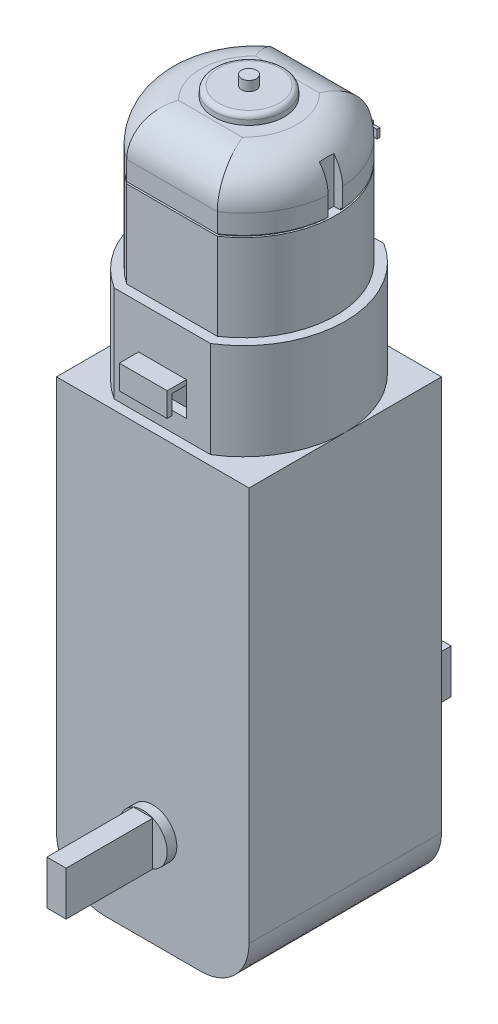
SolidWorks part; units mm, degrees
other "Camera1"
ref_plane "Front Plane" through (0, 0, 0) normal (0, 0, 1) x (1, 0, 0)
ref_plane "Top Plane" through (0, 0, 0) normal (0, 1, 0) x (1, 0, 0)
ref_plane "Right Plane" through (0, 0, 0) normal (1, 0, 0) x (0, 0, -1)
sketch "Sketch1" plane through (0, 0, 0) normal (0, 1, 0) x (1, 0, 0)
  line L1 (-5.5265, 6.0603) -> (14.4735, 6.0603)
  line L2 (-5.5265, 6.0603) -> (-5.5265, -13.9397)
  line L3 (-5.5265, -13.9397) -> (14.4735, -13.9397)
  line L4 (14.4735, 6.0603) -> (14.4735, -13.9397)
  dimension "D1" = 20
  dimension "D2" = 20
extrude "Boss-Extrude1" add sketch "Sketch1" along normal blind 46
sketch "Sketch2" plane through (0, 46, 0) normal (0, 1, 0) x (1, 0, 0)
  line L0 (14.4735, 6.0603) -> (-5.5265, 6.0603) construction
  line L1 (4.4735, 5.0603) -> (4.4735, 6.0603) construction
  line L2 (-0.5265, 5.0603) -> (9.4735, 5.0603)
  line L3 (14.4735, -3.9397) -> (-5.5265, -3.9397) construction
  line L4 (14.4735, -13.9397) -> (14.4735, 6.0603) construction
  line L5 (-5.5265, 6.0603) -> (-5.5265, -13.9397) construction
  line L6 (-0.5265, -12.9397) -> (9.4735, -12.9397)
  arc A0 (9.4735, 5.0603) -> (9.4735, -12.9397) centre (3.8735, -3.9397) cw
  arc A1 (-0.5265, -12.9397) -> (-0.5265, 5.0603) centre (5.0735, -3.9397) cw
  dimension "D1" = 10
  dimension "D2" = 1
extrude "Boss-Extrude2" add sketch "Sketch2" along normal blind 10
sketch "Sketch3" plane through (0, 56, 0) normal (0, 1, 0) x (1, 0, 0)
  line L4 (-0.2331, -11.9397) -> (9.1801, -11.9397)
  line L5 (9.1801, 4.0603) -> (-0.2331, 4.0603)
  line L6 (-0.2331, -11.9397) -> (9.1801, -11.9397)
  line L7 (9.1801, 4.0603) -> (-0.2331, 4.0603)
  arc A4 (-0.2331, 4.0603) -> (-0.2331, -11.9397) centre (5.0735, -3.9397) ccw
  arc A5 (9.1801, -11.9397) -> (9.1801, 4.0603) centre (3.8735, -3.9397) ccw
  arc A6 (-0.2331, 4.0603) -> (-0.2331, -11.9397) centre (5.0735, -3.9397) ccw
  arc A7 (9.1801, -11.9397) -> (9.1801, 4.0603) centre (3.8735, -3.9397) ccw
  dimension "D1" = 1
extrude "Cut-Extrude2" cut sketch "Sketch3" against normal blind 12
sketch "Sketch5" plane through (0, 44, 0) normal (0, 1, 0) x (1, 0, 0)
  line L0 (14.4735, -13.9397) -> (14.4735, -3.9397) construction
  line L1 (-4.5265, 5.0603) -> (13.4735, 5.0603)
  line L2 (-4.5265, 5.0603) -> (-4.5265, -12.9397)
  line L3 (-4.5265, -12.9397) -> (13.4735, -12.9397)
  line L4 (13.4735, 5.0603) -> (13.4735, -12.9397)
  line L5 (-5.5265, -3.9397) -> (-5.5265, -13.9397) construction
  line L6 (14.4735, 6.0603) -> (-5.5265, 6.0603) construction
  line L7 (-5.5265, -13.9397) -> (14.4735, -13.9397) construction
  dimension "D1" = 1
  dimension "D2" = 1
  dimension "D3" = 1
  dimension "D4" = 1
extrude "Cut-Extrude3" cut sketch "Sketch5" against normal blind 42
sketch "Sketch6" plane through (0, 0, 12.9397) normal (0, 0, 1) x (1, 0, 0)
  line L0 (4.4735, 56) -> (4.4735, 51) construction
  line L1 (-0.5265, 56) -> (9.4735, 56) construction
  line L2 (6.9735, 51) -> (1.9735, 51) construction
  line L8 (6.9735, 51) -> (1.9735, 51)
  line L9 (6.9735, 51) -> (6.9735, 48)
  line L10 (6.9735, 48) -> (1.9735, 48)
  line L11 (1.9735, 51) -> (1.9735, 48)
  point P6 (4.4735, 51)
  dimension "D1" = 5
  dimension "D2" = 5
  dimension "D3" = 3
extrude "Cut-Extrude4" cut sketch "Sketch6" against normal blind 20
sketch "Sketch7" plane through (0, 0, 12.9397) normal (0, 0, 1) x (1, 0, 0)
  line L1 (6.9735, 51) -> (2.002, 51)
  line L2 (6.9735, 51) -> (6.9735, 51.5)
  line L3 (6.9735, 51.5) -> (2.002, 51.5)
  line L4 (2.002, 51) -> (2.002, 51.5)
  dimension "D1" = 0.5
extrude "Boss-Extrude5" add sketch "Sketch7" along normal blind 2
sketch "Sketch8" plane through (0, 51, 0) normal (0, -1, 0) x (1, 0, 0)
  line L0 (6.9735, 14.9397) -> (6.9735, 12.9397) construction
  line L1 (2.002, 14.9397) -> (6.9735, 14.9397)
  line L2 (2.002, 14.9397) -> (2.002, 14.4397)
  line L3 (2.002, 14.4397) -> (6.9735, 14.4397)
  line L4 (6.9735, 14.9397) -> (6.9735, 14.4397)
  dimension "D1" = 0.5
extrude "Boss-Extrude6" add sketch "Sketch8" along normal blind 2
sketch "Sketch10" plane through (0, 0, -5.0603) normal (0, 0, -1) x (-1, 0, 0)
  line L2 (-6.9735, 51) -> (-1.9697, 51)
  line L3 (-6.9735, 51) -> (-6.9735, 51.5)
  line L4 (-6.9735, 51.5) -> (-1.9697, 51.5)
  line L5 (-1.9697, 51) -> (-1.9697, 51.5)
  dimension "D1" = 0.5
extrude "Boss-Extrude7" add sketch "Sketch10" along normal blind 2
sketch "Sketch11" plane through (0, 51, 0) normal (0, -1, 0) x (1, 0, 0)
  line L0 (1.9697, -7.0603) -> (1.9697, -5.0603) construction
  line L1 (6.9735, -7.0603) -> (1.9697, -7.0603)
  line L2 (6.9735, -7.0603) -> (6.9735, -6.5603)
  line L3 (6.9735, -6.5603) -> (1.9697, -6.5603)
  line L4 (1.9697, -7.0603) -> (1.9697, -6.5603)
  dimension "D1" = 0.5
extrude "Boss-Extrude8" add sketch "Sketch11" along normal blind 2
sketch "Sketch17" plane through (0, 0, -6.0603) normal (0, 0, -1) x (-1, 0, 0)
  line L0 (-4.4735, 46) -> (-4.4735, 42.544) construction
  line L1 (-14.4735, 46) -> (5.5265, 46) construction
  circle A0 centre (-9.3166, 43.6587) radius 1.5
  circle A1 centre (0.3696, 43.6587) radius 1.5
extrude "Cut-Extrude15" cut sketch "Sketch17" against normal blind 8
sketch "Sketch19" plane through (0, 0, -5.0603) normal (0, 0, 1) x (1, 0, 0)
  circle A0 centre (-0.3696, 43.6587) radius 1.5 construction
  circle A1 centre (-0.3696, 43.6587) radius 1.5
  circle A2 centre (9.3166, 43.6587) radius 1.5 construction
  circle A3 centre (9.3166, 43.6587) radius 1.5
extrude "Boss-Extrude15" add sketch "Sketch19" against normal blind 0.5 draft 18 separate body
fillet "Fillet3" radius 0.2 1 edges at (0.9679, 43.6587, -5.5603)
fillet "Fillet4" radius 0.2 1 edges at (10.6542, 43.6587, -5.5603)
sketch "Sketch20" plane through (0, 0, -5.5603) normal (0, 0, -1) x (-1, 0, 0)
  line L0 (0.2802, 43.5844) -> (-0.1304, 43.5844)
  line L2 (0.3696, 43.6587) -> (-0.1304, 43.6587) construction
  line L4 (0.3696, 43.6587) -> (0.3696, 44.1587) construction
  line L7 (0.8696, 43.6587) -> (-0.1304, 43.6587) construction
  line L8 (0.8696, 43.5844) -> (0.459, 43.5844)
  line L9 (0.8696, 43.733) -> (0.459, 43.733)
  line L10 (0.3696, 44.1587) -> (0.3696, 43.1587) construction
  line L11 (0.459, 44.1587) -> (0.459, 43.733)
  line L12 (0.2802, 44.1587) -> (0.2802, 43.733)
  line L13 (0.459, 43.5844) -> (0.459, 43.1587)
  line L14 (0.2802, 43.733) -> (-0.1304, 43.733)
  line L15 (0.2802, 43.5844) -> (0.2802, 43.1587)
  arc A0 (0.8696, 43.5844) -> (0.8696, 43.733) centre (0.8696, 43.6587) ccw
  arc A1 (-0.1304, 43.733) -> (-0.1304, 43.5844) centre (-0.1304, 43.6587) ccw
  arc A2 (0.459, 44.1587) -> (0.2802, 44.1587) centre (0.3696, 44.1587) ccw
  arc A3 (0.2802, 43.1587) -> (0.459, 43.1587) centre (0.3696, 43.1587) ccw
  point P3 (0.3696, 43.6587)
  point P11 (0.3696, 43.6587)
  dimension "D1" = 0.5
  dimension "D2" = 0.5
  dimension "D3" = 0.5
  dimension "D4" = 0.5
extrude "Cut-Extrude18" cut sketch "Sketch20" against normal blind 0.2 draft 11
sketch "Sketch21" plane through (0, 0, -5.5603) normal (0, 0, -1) x (-1, 0, 0)
  line L0 (-9.4729, 43.8332) -> (-9.8835, 43.8332)
  line L1 (-9.3835, 43.9075) -> (-9.8835, 43.9075) construction
  line L2 (-9.3835, 43.9075) -> (-9.3835, 44.4075) construction
  line L3 (-8.8835, 43.9075) -> (-9.8835, 43.9075) construction
  line L4 (-8.8835, 43.8332) -> (-9.2941, 43.8332)
  line L5 (-8.8835, 43.9818) -> (-9.2941, 43.9818)
  line L6 (-9.3835, 44.4075) -> (-9.3835, 43.4075) construction
  line L7 (-9.2941, 44.4075) -> (-9.2941, 43.9818)
  line L8 (-9.4729, 44.4075) -> (-9.4729, 43.9818)
  line L9 (-9.2941, 43.8332) -> (-9.2941, 43.4075)
  line L10 (-9.4729, 43.9818) -> (-9.8835, 43.9818)
  line L11 (-9.4729, 43.8332) -> (-9.4729, 43.4075)
  arc A0 (-8.8835, 43.8332) -> (-8.8835, 43.9818) centre (-8.8835, 43.9075) ccw
  arc A1 (-9.8835, 43.9818) -> (-9.8835, 43.8332) centre (-9.8835, 43.9075) ccw
  arc A2 (-9.2941, 44.4075) -> (-9.4729, 44.4075) centre (-9.3835, 44.4075) ccw
  arc A3 (-9.4729, 43.4075) -> (-9.2941, 43.4075) centre (-9.3835, 43.4075) ccw
  point P2 (-9.3835, 43.9075)
  point P10 (-9.3835, 43.9075)
  dimension "D1" = 0.5
  dimension "D2" = 0.5
  dimension "D3" = 0.5
  dimension "D4" = 0.5
extrude "Cut-Extrude19" cut sketch "Sketch21" against normal blind 0.2 draft 11
sketch "Sketch22" plane through (0, 56, 0) normal (0, 1, 0) x (1, 0, 0)
  line L0 (9.1801, 4.0603) -> (-0.2331, 4.0603) construction
  line L1 (-0.2331, -11.9397) -> (9.1801, -11.9397) construction
  line L2 (9.1801, 4.0603) -> (-0.2331, 4.0603)
  line L3 (-0.2331, -11.9397) -> (9.1801, -11.9397)
  arc A0 (9.1801, -11.9397) -> (9.1801, 4.0603) centre (3.8735, -3.9397) ccw construction
  arc A1 (-0.2331, 4.0603) -> (-0.2331, -11.9397) centre (5.0735, -3.9397) ccw construction
  arc A2 (9.1801, -11.9397) -> (9.1801, 4.0603) centre (3.8735, -3.9397) ccw
  arc A3 (-0.2331, 4.0603) -> (-0.2331, -11.9397) centre (5.0735, -3.9397) ccw
extrude "Boss-Extrude16" add sketch "Sketch22" along normal blind 9 separate body
sketch "Sketch23" plane through (0, 65, 0) normal (0, 1, 0) x (1, 0, 0)
  line L2 (9.1801, 4.0603) -> (-0.2331, 4.0603)
  line L3 (-0.2331, -11.9397) -> (9.1801, -11.9397)
  line L4 (9.1801, 4.0603) -> (-0.2331, 4.0603)
  line L5 (-0.2331, -11.9397) -> (9.1801, -11.9397)
  arc A2 (9.1801, -11.9397) -> (9.1801, 4.0603) centre (3.8735, -3.9397) ccw
  arc A3 (-0.2331, 4.0603) -> (-0.2331, -11.9397) centre (5.0735, -3.9397) ccw
  arc A4 (9.1801, -11.9397) -> (9.1801, 4.0603) centre (3.8735, -3.9397) ccw
  arc A5 (-0.2331, 4.0603) -> (-0.2331, -11.9397) centre (5.0735, -3.9397) ccw
  dimension "D1" = 0
extrude "Boss-Extrude18" add sketch "Sketch23" along normal blind 0.01
sketch "Sketch24" plane through (0, 65.01, 0) normal (0, 1, 0) x (1, 0, 0)
  line L4 (9.1194, 3.8603) -> (-0.1725, 3.8603)
  line L5 (-0.1725, -11.7397) -> (9.1194, -11.7397)
  line L6 (9.1194, 3.8603) -> (-0.1725, 3.8603)
  line L7 (-0.1725, -11.7397) -> (9.1194, -11.7397)
  arc A4 (9.1194, -11.7397) -> (9.1194, 3.8603) centre (3.8735, -3.9397) ccw
  arc A5 (-0.1725, 3.8603) -> (-0.1725, -11.7397) centre (5.0735, -3.9397) ccw
  arc A6 (9.1194, -11.7397) -> (9.1194, 3.8603) centre (3.8735, -3.9397) ccw
  arc A7 (-0.1725, 3.8603) -> (-0.1725, -11.7397) centre (5.0735, -3.9397) ccw
  dimension "D1" = 0.2
extrude "Boss-Extrude20" add sketch "Sketch24" along normal blind 0.2
sketch "Sketch25" plane through (0, 65.21, 0) normal (0, 1, 0) x (1, 0, 0)
  line L2 (9.1801, 4.0603) -> (-0.2331, 4.0603)
  line L3 (-0.2331, -11.9397) -> (9.1801, -11.9397)
  line L4 (9.1801, 4.0603) -> (-0.2331, 4.0603)
  line L5 (-0.2331, -11.9397) -> (9.1801, -11.9397)
  arc A2 (9.1801, -11.9397) -> (9.1801, 4.0603) centre (3.8735, -3.9397) ccw
  arc A3 (-0.2331, 4.0603) -> (-0.2331, -11.9397) centre (5.0735, -3.9397) ccw
  arc A4 (9.1801, -11.9397) -> (9.1801, 4.0603) centre (3.8735, -3.9397) ccw
  arc A5 (-0.2331, 4.0603) -> (-0.2331, -11.9397) centre (5.0735, -3.9397) ccw
  dimension "D1" = 0
extrude "Boss-Extrude21" add sketch "Sketch25" along normal blind 6
fillet "Fillet5" radius 4 4 edges at (4.4735, 71.21, -4.0603) (13.4735, 71.21, 3.9397) (-4.5265, 71.21, 3.9397) (4.4735, 71.21, 11.9397)
sketch "Sketch28" plane through (0, 71.21, 0) normal (0, 1, 0) x (1, 0, 0)
  line L0 (4.4735, -7.9397) -> (4.4735, 0.0603) construction
  line L1 (1.1543, -7.9397) -> (7.7927, -7.9397) construction
  line L2 (7.7927, 0.0603) -> (1.1543, 0.0603) construction
  line L3 (9.4735, -3.9397) -> (-0.5265, -3.9397) construction
  arc A0 (7.7927, -7.9397) -> (7.7927, 0.0603) centre (3.8735, -3.9397) ccw construction
  arc A1 (1.1543, 0.0603) -> (1.1543, -7.9397) centre (5.0735, -3.9397) ccw construction
  circle A2 centre (4.4735, -3.9397) radius 3.6608
extrude "Boss-Extrude22" add sketch "Sketch28" along normal blind 1
fillet "Fillet6" radius 0.5 1 edges at (4.4735, 72.21, 7.6005)
ref_plane "Plane1" through (0, 65.01, 0) normal (0, 1, 0) x (1, 0, 0)
sketch "Sketch30" plane through (0, 65.01, 0) normal (0, 1, 0) x (1, 0, 0)
  line L0 (13.4735, -3.9397) -> (3.8735, -3.9397) construction
  line L1 (13.4735, -3.1897) -> (13.4735, -4.6897) construction
  line L2 (4.4735, 4.0603) -> (4.4735, -1.2422) construction
  line L3 (13.4735, -3.1897) -> (12.5374, -3.1897)
  line L4 (13.4735, -3.1897) -> (13.4735, -4.6897)
  line L5 (13.4735, -4.6897) -> (12.5374, -4.6897)
  line L6 (12.5374, -3.1897) -> (12.5374, -4.6897)
  line L7 (9.1801, 4.0603) -> (-0.2331, 4.0603) construction
  line L8 (-4.5265, -3.1897) -> (-4.5265, -4.6897)
  line L9 (-4.5265, -4.6897) -> (-3.5904, -4.6897)
  line L10 (-4.5265, -3.1897) -> (-3.5904, -3.1897)
  line L11 (-3.5904, -3.1897) -> (-3.5904, -4.6897)
  arc A2 (9.1801, -11.9397) -> (9.1801, 4.0603) centre (3.8735, -3.9397) ccw construction
  point P2 (13.4735, -3.9397)
  point P4 (4.4735, 4.8753)
  dimension "D1" = 1.5
extrude "Cut-Extrude23" cut sketch "Sketch30" along normal blind 11
sketch "Sketch34" plane through (0, 72.21, 0) normal (0, 1, 0) x (1, 0, 0)
  circle A0 centre (4.4735, -3.9397) radius 0.7702
extrude "Boss-Extrude25" add sketch "Sketch34" along normal blind 1
sketch "Sketch35" plane through (0, 0, -4.0603) normal (0, 0, -1) x (-1, 0, 0)
  line L1 (-8.3917, 66.5343) -> (-0.671, 66.5343)
  line L2 (-8.3917, 66.5343) -> (-8.3917, 65.6515)
  line L3 (-8.3917, 65.6515) -> (-0.671, 65.6515)
  line L4 (-0.671, 66.5343) -> (-0.671, 65.6515)
extrude "Boss-Extrude26" add sketch "Sketch35" along normal blind 1
sketch "Sketch36" plane through (0.671, 0, 0) normal (-1, 0, 0) x (0, 0, 1)
  line L0 (-5.0603, 66.5343) -> (-4.0603, 66.5343) construction
  line L1 (-4.7314, 66.5343) -> (-4.4504, 66.5343)
  line L2 (-4.7314, 66.5343) -> (-4.7314, 65.6515)
  line L3 (-4.7314, 65.6515) -> (-4.4504, 65.6515)
  line L4 (-4.4504, 66.5343) -> (-4.4504, 65.6515)
  line L5 (-5.0603, 65.6515) -> (-4.0603, 65.6515) construction
extrude "Boss-Extrude27" add sketch "Sketch36" along normal blind 1
sketch "Sketch37" plane through (8.3917, 0, 0) normal (1, 0, 0) x (0, 0, -1)
  line L1 (4.4504, 66.5343) -> (4.7314, 66.5343)
  line L2 (4.4504, 66.5343) -> (4.4504, 65.6515)
  line L3 (4.4504, 65.6515) -> (4.7314, 65.6515)
  line L4 (4.7314, 66.5343) -> (4.7314, 65.6515)
extrude "Boss-Extrude28" add sketch "Sketch37" along normal blind 1
fillet "Fillet7" radius 5 2 edges at (14.4735, 0, 3.9397) (-5.5265, 0, 3.9397)
sketch "Sketch41" plane through (0, 0, -6.0603) normal (0, 0, -1) x (-1, 0, 0)
  line L0 (-4.4735, 0) -> (-4.4735, 10) construction
  line L1 (-9.4735, 0) -> (0.5265, 0) construction
  circle A0 centre (-4.4735, 10) radius 2.5
  dimension "D2" = 5
  dimension "D1" = 10
extrude "Boss-Extrude29" add sketch "Sketch41" along normal blind 1
sketch "Sketch42" plane through (0, 0, -7.0603) normal (0, 0, -1) x (-1, 0, 0)
  line L1 (-5.4735, 12.2913) -> (-3.4735, 12.2913)
  line L2 (-5.4735, 12.2913) -> (-5.4735, 7.7087)
  line L3 (-5.4735, 7.7087) -> (-3.4735, 7.7087)
  line L4 (-3.4735, 12.2913) -> (-3.4735, 7.7087)
  circle A0 centre (-4.4735, 10) radius 2.5 construction
  circle A1 centre (-4.4735, 10) radius 2.5 construction
  dimension "D1" = 1
  dimension "D2" = 1
extrude "Boss-Extrude30" add sketch "Sketch42" along normal blind 9
sketch "Sketch43" plane through (0, 0, 13.9397) normal (0, 0, 1) x (1, 0, 0)
  circle A0 centre (4.4735, 10) radius 2.5
extrude "Boss-Extrude32" add sketch "Sketch43" along normal blind 1
sketch "Sketch45" plane through (0, 0, 14.9397) normal (0, 0, 1) x (1, 0, 0)
  line L1 (3.4735, 12.2913) -> (5.4735, 12.2913)
  line L2 (3.4735, 12.2913) -> (3.4735, 7.7087)
  line L3 (3.4735, 7.7087) -> (5.4735, 7.7087)
  line L4 (5.4735, 12.2913) -> (5.4735, 7.7087)
extrude "Boss-Extrude33" add sketch "Sketch45" along normal blind 9
